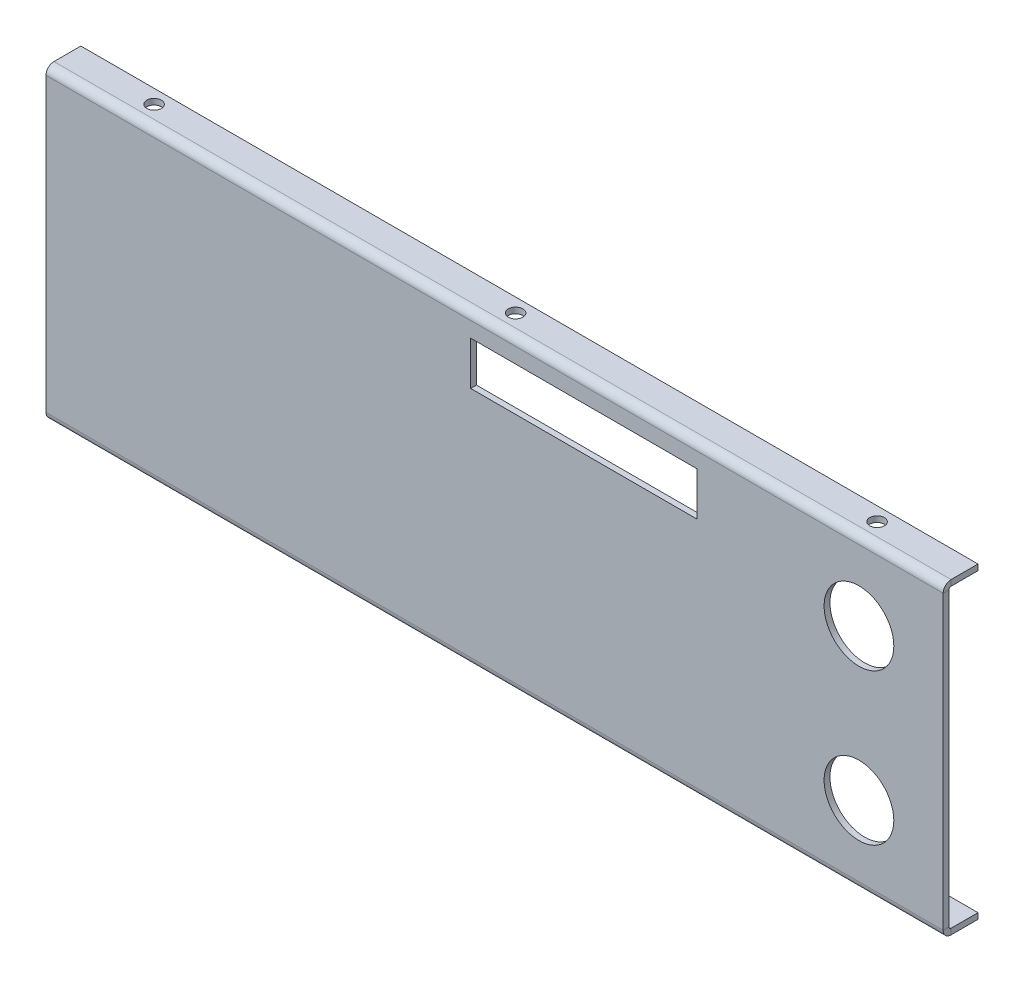
SolidWorks part; units mm, degrees
note: The reader was unsure of these and kept them because the rebuilt part matched: flange length of "Edge-Flange1".
material "ASTM A36 Steel"
ref_plane "Front Plane" through (0, 0, 0) normal (0, 0, 1) x (1, 0, 0)
ref_plane "Top Plane" through (0, 0, 0) normal (0, 1, 0) x (1, 0, 0)
ref_plane "Right Plane" through (0, 0, 0) normal (1, 0, 0) x (0, 0, -1)
sketch "Sketch2" plane through (0, 0, 0) normal (0, 0, 1) x (1, 0, 0)
  line L0 (0, 158.2293) -> (0, -58.0707) construction
  line L1 (-154.5, 106) -> (154.5, 106)
  line L2 (-154.5, 106) -> (-154.5, 0)
  line L3 (-154.5, 0) -> (154.5, 0)
  line L4 (154.5, 106) -> (154.5, 0)
  dimension "D1" = 309
  dimension "D2" = 106
base flange "Base-Flange1" sketch "Sketch2" thickness 2 reverse thickness direction no parameters "D1"=0.7366
edge flange "Edge-Flange1" sketch "Sketch11" flange profiles "Sketch11", "Sketch12" flange angle 90 flange length 12 flange position material inside bend radius 0.7366 thickness 2 relief rectangular parameters "D6"=10, "D8"=1
sketch "Sketch11" plane through (0, 0, -2) normal (0, -1, 0) x (-1, 0, 0)
  line L0 (154.5, 0) -> (-154.5, 0) construction
  line L1 (154.5, 0) -> (-154.5, 0)
  line L2 (-154.5, 0) -> (-154.5, 10)
  line L3 (-154.5, 10) -> (154.5, 10)
  line L4 (154.5, 10) -> (154.5, 0)
sketch "Sketch12" plane through (0, 106, -2) normal (0, 1, 0) x (1, 0, 0)
  line L0 (154.5, 0) -> (-154.5, 0) construction
  line L1 (154.5, 0) -> (-154.5, 0)
  line L2 (-154.5, 0) -> (-154.5, 10)
  line L3 (-154.5, 10) -> (154.5, 10)
  line L4 (154.5, 10) -> (154.5, 0)
bend "EdgeBend1" bend radius 0.7366 bend angle 90 parameters "D5"=1
bend "EdgeBend2" bend radius 0.7366 bend angle 90 parameters "D5"=2
sketch "Sketch13" plane through (0, 0, 0) normal (0, 0, 1) x (1, 0, 0)
  line L0 (142.5, 93) -> (142.5, 2.7366) construction
  line L1 (108.5, 96) -> (142.5, 96) construction
  line L2 (108.5, 96) -> (108.5, 62) construction
  line L3 (108.5, 62) -> (142.5, 62) construction
  line L4 (142.5, 96) -> (142.5, 62) construction
  line L5 (-154.5, 2.7366) -> (154.5, 2.7366) construction
  line L6 (121.9729, 62) -> (146.7059, 62) construction
  line L7 (139.5, 62) -> (111.5, 62) construction
  line L8 (112.4891, 96) -> (104.5927, 96) construction
  line L9 (139.5, 96) -> (111.5, 96) construction
  line L10 (108.5, 87.3829) -> (108.5, 3.6213) construction
  line L11 (108.5, 93) -> (108.5, 65) construction
  line L12 (115.8677, 44) -> (151.2571, 44) construction
  line L13 (139.5, 44) -> (111.5, 44) construction
  line L14 (121.9729, 52.7508) -> (181.5305, 52.7508) construction
  line L15 (123.5056, 10) -> (97.6711, 10) construction
  line L16 (108.5, 44) -> (142.5, 44) construction
  line L17 (108.5, 44) -> (108.5, 10) construction
  line L18 (108.5, 10) -> (142.5, 10) construction
  line L19 (142.5, 44) -> (142.5, 10) construction
  line L20 (111.5, 10) -> (139.5, 10) construction
  line L21 (108.5, 62) -> (142.5, 96) construction
  line L22 (142.5, 44) -> (108.5, 10) construction
  circle A0 centre (125.5, 79) radius 12
  circle A1 centre (125.5, 27) radius 12
  dimension "D1" = 24
extrude "Cut-Extrude1" cut sketch "Sketch13" against normal through all both normal cut yes
sketch "Sketch14" plane through (0, 0, 0) normal (0, 0, 1) x (1, 0, 0)
  line L1 (-8.2404, 98) -> (69.7867, 98)
  line L2 (-8.2404, 98) -> (-8.2404, 83)
  line L3 (-8.2404, 83) -> (69.7867, 83)
  line L4 (69.7867, 98) -> (69.7867, 83)
extrude "Cut-Extrude2" cut sketch "Sketch14" against normal through all both normal cut yes
sketch "Sketch15" plane through (0, 106, 0) normal (0, 1, 0) x (1, 0, 0)
  circle A0 centre (124.5, 7.2366) radius 2.5
  circle A1 centre (0, 7.2366) radius 2.5
  circle A2 centre (-124.5, 7.2366) radius 2.5
extrude "Cut-Extrude3" cut sketch "Sketch15" against normal through all both and the other way through all normal cut yes
sketch "Bend-Lines1" [suppressed] plane through (0, 0, 0) normal (0, 1, 0) x (1, 0, 0)
sketch "Bounding-Box1" [suppressed] plane through (0, 0, 0) normal (0, 1, 0) x (1, 0, 0)
sheet metal parameters "Sheet-Metal1" thickness 2 parameters "D1"=0.7366
flat pattern "Flat-Pattern1" [suppressed]
sketch "Bend-Lines2" plane through (0, 0, 0) normal (0, 1, 0) x (1, 0, 0)
sketch3d "Bounding-Box2" [suppressed]
  line L0 (154.5, 0, 0) -> (-154.5, 0, 0) construction
  line L1 (154.5, 106, 0) -> (-154.5, 106, 0) construction
  line L2 (154.5, 0, 0) -> (154.5, 106, 0) construction
  line L3 (-154.5, 0, 0) -> (-154.5, 106, 0) construction
sheet metal parameters "Sheet-Metal2" thickness 2 parameters "D1"=0.7366
flat pattern "Flat-Pattern1"
sketch "Bend-Lines2" plane through (0, 0, 0) normal (0, 0, 1) x (1, 0, 0)
  line L0 (154.5, 104.6273) -> (-154.5, 104.6273) construction
  line L1 (-154.5, 1.3727) -> (154.5, 1.3727) construction
  line L2 (154.5, 104.6273) -> (-154.5, 104.6273) construction
  line L3 (-154.5, 1.3727) -> (154.5, 1.3727) construction
sketch3d "Bounding-Box2" [suppressed]
  line L0 (-154.5, -9.2546, 0) -> (154.5, -9.2546, 0) construction
  line L1 (-154.5, 115.2546, 0) -> (154.5, 115.2546, 0) construction
  line L2 (-154.5, -9.2546, 0) -> (-154.5, 115.2546, 0) construction
  line L3 (154.5, -9.2546, 0) -> (154.5, 115.2546, 0) construction
bend of the flat pattern "Flatten-<EdgeBend1>1"
bend of the flat pattern "Flatten-<EdgeBend2>1"
sheet metal parameters "Sheet-Metal3" thickness 2 parameters "D1"=0.7366
flat pattern "Flat-Pattern1"
sketch "Bend-Lines2" plane through (0, 0, 0) normal (0, 0, 1) x (1, 0, 0)
  line L0 (154.5, 104.6273) -> (-154.5, 104.6273) construction
  line L1 (-154.5, 1.3727) -> (154.5, 1.3727) construction
  line L2 (154.5, 104.6273) -> (-154.5, 104.6273) construction
  line L3 (-154.5, 1.3727) -> (154.5, 1.3727) construction
sketch3d "Bounding-Box2" [suppressed]
  line L0 (-154.5, -9.2546, 0) -> (154.5, -9.2546, 0) construction
  line L1 (-154.5, 115.2546, 0) -> (154.5, 115.2546, 0) construction
  line L2 (-154.5, -9.2546, 0) -> (-154.5, 115.2546, 0) construction
  line L3 (154.5, -9.2546, 0) -> (154.5, 115.2546, 0) construction
bend of the flat pattern "Flatten-<EdgeBend1>1"
bend of the flat pattern "Flatten-<EdgeBend2>1"
sheet metal parameters "Sheet-Metal4" thickness 2 parameters "D1"=0.7366
flat pattern "Flat-Pattern1"
sketch "Bend-Lines2" plane through (0, 0, 0) normal (0, 0, 1) x (1, 0, 0)
  line L0 (154.5, 104.6273) -> (-154.5, 104.6273) construction
  line L1 (-154.5, 1.3727) -> (154.5, 1.3727) construction
  line L2 (154.5, 104.6273) -> (-154.5, 104.6273) construction
  line L3 (-154.5, 1.3727) -> (154.5, 1.3727) construction
sketch3d "Bounding-Box2" [suppressed]
  line L0 (-154.5, -9.2546, 0) -> (154.5, -9.2546, 0) construction
  line L1 (-154.5, 115.2546, 0) -> (154.5, 115.2546, 0) construction
  line L2 (-154.5, -9.2546, 0) -> (-154.5, 115.2546, 0) construction
  line L3 (154.5, -9.2546, 0) -> (154.5, 115.2546, 0) construction
bend of the flat pattern "Flatten-<EdgeBend1>1"
bend of the flat pattern "Flatten-<EdgeBend2>1"
sheet metal parameters "Sheet-Metal5" thickness 2 parameters "D1"=0.7366
flat pattern "Flat-Pattern1"
sketch "Bend-Lines2" plane through (0, 0, 0) normal (0, 0, 1) x (1, 0, 0)
  line L0 (154.5, 104.6273) -> (-154.5, 104.6273) construction
  line L1 (-154.5, 1.3727) -> (154.5, 1.3727) construction
  line L2 (154.5, 104.6273) -> (-154.5, 104.6273) construction
  line L3 (-154.5, 1.3727) -> (154.5, 1.3727) construction
sketch3d "Bounding-Box2" [suppressed]
  line L0 (-154.5, -9.2546, 0) -> (154.5, -9.2546, 0) construction
  line L1 (-154.5, 115.2546, 0) -> (154.5, 115.2546, 0) construction
  line L2 (-154.5, -9.2546, 0) -> (-154.5, 115.2546, 0) construction
  line L3 (154.5, -9.2546, 0) -> (154.5, 115.2546, 0) construction
bend of the flat pattern "Flatten-<EdgeBend1>1"
bend of the flat pattern "Flatten-<EdgeBend2>1"
